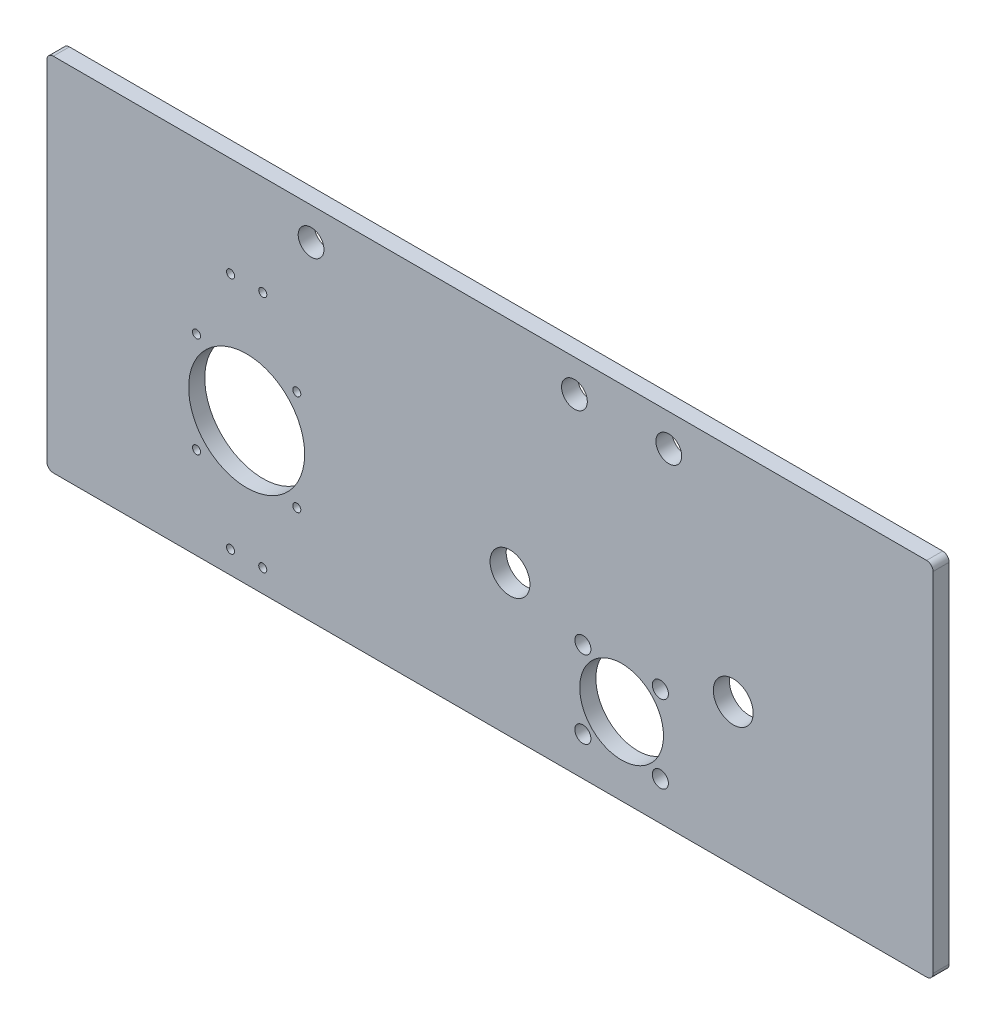
SolidWorks part; units mm, degrees
ref_plane "Спереди" through (0, 0, 0) normal (0, 0, 1) x (1, 0, 0)
ref_plane "Сверху" through (0, 0, 0) normal (0, 1, 0) x (1, 0, 0)
ref_plane "Справа" through (0, 0, 0) normal (1, 0, 0) x (0, 0, -1)
sketch "Эскиз1" plane through (0, 0, 0) normal (0, 0, 1) x (1, 0, 0)
  line L0 (-12.0208, 12.0208) -> (0, 0) construction
  line L1 (-178.359, 88) -> (96.641, 88)
  line L2 (-178.359, 88) -> (-178.359, -24)
  line L3 (-178.359, -24) -> (96.641, -24)
  line L4 (96.641, 88) -> (96.641, -24)
  line L5 (0, 0) -> (0, 88) construction
  line L6 (-34.641, 20) -> (0, 0) construction
  circle A0 centre (0, 0) radius 13
  circle A1 centre (-12.0208, 12.0208) radius 2.5
  circle A2 centre (12.0208, 12.0208) radius 2.5
  circle A3 centre (12.0208, -12.0208) radius 2.5
  circle A4 centre (-12.0208, -12.0208) radius 2.5
  circle A5 centre (-34.641, 20) radius 6.1833
  circle A6 centre (34.641, 20) radius 6.1833
  circle A7 centre (-116.359, 20) radius 18
  circle A8 centre (-14.641, 78) radius 4
  circle A9 centre (14.641, 78) radius 4
  circle A10 centre (-96.359, 78) radius 4
  circle A11 centre (-116.359, 20) radius 18 construction
  point P19 (0, 0)
  dimension "D2" = 5
  dimension "D4" = 26
  dimension "D9" = 8
  dimension "D1" = 45
  dimension "D3" = 17
  dimension "D6" = 58
  dimension "D7" = 20
  dimension "D8" = 20
  dimension "D10" = 10
  dimension "D12" = 40
  dimension "D13" = 20
  dimension "D14" = 275
  dimension "D15" = 82
  dimension "D16" = 82
  dimension "D11" = 112
  dimension "D5" = 4
extrude "Бобышка-Вытянуть1" add sketch "Эскиз1" along normal blind 5
hole_wizard "Отверстие обработанное метчиком M32" positions "Эскиз2" profile "Эскиз4" tap size "M3" standard "ISO" end condition through all
sketch "Эскиз2" plane through (0, 0, 0) normal (0, 0, -1) x (-1, 0, 0)
  point P0 (111.359, 57)
  point P3 (121.359, 57)
  point P6 (111.359, -17)
  point P9 (121.359, -17)
sketch "Эскиз4" plane through (-111.359, 57, 0) normal (1, 0, 0) x (0, 1, 0)
  line L0 (0, 0) -> (0, 5)
  line L1 (0, 5) -> (1.25, 5)
  line L2 (1.25, 5) -> (1.25, 0)
  line L5 (1.25, 0) -> (0, 0)
  line L11 (0, -6.35) -> (0, 107.95) construction
  dimension "Диаметр проходного сверла" = 2.5
  dimension "Глубина проходного сверла" = 5
cosmetic thread "Отверстие резьбы1" parameters "D2"=3
cosmetic thread "Отверстие резьбы2" parameters "D2"=3
cosmetic thread "Отверстие резьбы3" parameters "D2"=3
cosmetic thread "Отверстие резьбы4" parameters "D2"=3
fillet "Скругление1" radius 2 4 edges at (-178.359, -24, 2.5) (96.641, -24, 2.5) (96.641, 88, 2.5) (-178.359, 88, 2.5)
hole_wizard "Отверстие обработанное метчиком M35" positions "Эскиз12" profile "Эскиз13" tap size "M3" standard "DIN" end condition up to next
sketch "Эскиз12" plane through (0, 0, 5) normal (0, 0, 1) x (1, 0, 0)
  point P0 (-100.8026, 35.5563)
sketch "Эскиз13" plane through (-100.8026, 35.5563, 5) normal (1, 0, 0) x (0, -1, 0)
  line L0 (0, 0) -> (0, 5)
  line L1 (0, 5) -> (1.25, 5)
  line L2 (1.25, 5) -> (1.25, 0)
  line L5 (1.25, 0) -> (0, 0)
  line L11 (0, -6.35) -> (0, 107.95) construction
  dimension "Диаметр проходного сверла" = 2.5
  dimension "Глубина проходного сверла" = 5
pattern_circular "Круговой массив1" count 4 over 360 about axis through (-116.359, 20, 0) along (0, 0, 1) of "Отверстие обработанное метчиком M35"
sketch "Эскиз5" plane through (0, 0, 5) normal (0, 0, 1) x (1, 0, 0)
  line L0 (-178.359, 66) -> (96.641, 66)
  line L1 (-178.359, 86) -> (-178.359, -22) construction
  line L2 (96.641, -22) -> (96.641, 86) construction
  line L3 (-158.359, 78) -> (-158.359, -24)
  line L4 (-176.359, -24) -> (94.641, -24) construction
  line L5 (-76.641, 78) -> (-76.641, -24)
  line L6 (76.641, 78) -> (76.641, -24)
  circle A0 centre (14.641, 78) radius 4 construction
  circle A1 centre (14.641, 78) radius 4 construction
  circle A2 centre (14.641, 78) radius 62 construction
  circle A3 centre (-14.641, 78) radius 62 construction
  circle A4 centre (-96.359, 78) radius 62 construction
  dimension "D2" = 124
  dimension "D1" = 12
ref_plane "Плоскость1" through (0, 66, 0) normal (0, 1, 0) x (1, 0, 0)
ref_plane "Плоскость2" through (-158.359, 0, 0) normal (1, 0, 0) x (0, 0, -1)
ref_plane "Плоскость3" through (-76.641, 0, 0) normal (1, 0, 0) x (0, 0, -1)
ref_plane "Плоскость4" through (76.641, 0, 0) normal (1, 0, 0) x (0, 0, -1)
equation "\"Диаметр резьбы редуктора\" = 4  'Диаметр резьбы на фланце"
equation "\"Глубина резьбы редуктора\" = 7  'Диаметр резьбы на фланце"
equation "\"Диаметр окружности расположения редуктора\" = 34  'Диаметр расположения резьбы на фланце"
equation "\"Диаметр бурта редуктора\" = 26  'Диаметр бурта на фланце (Посадка h7)"
equation "\"Угл сдвига редуктора\" = 45"
equation "\"D1@Эскиз1\"=\"Угл сдвига редуктора\""
equation "\"D2@Эскиз1\"=\"Диаметр резьбы редуктора\"+1"
equation "\"D3@Эскиз1\"=\"Диаметр окружности расположения редуктора\"/2"
equation "\"D4@Эскиз1\"=\"Диаметр бурта редуктора\""
equation "\"Толщина пластины\" = 5"
equation "\"Межосевое прижима Вертикаль\" = 18  '!!!"
equation "\"Межосевое прижима Горизонталь\" = 20  '!!!"
equation "\"D7@Эскиз1\"=\"Межосевое прижима Горизонталь\""
equation "\"D8@Эскиз1\"=\"Межосевое прижима Горизонталь\""
equation "\"D1@Бобышка-Вытянуть1\"=\"Толщина пластины\""
equation "\"D6@Эскиз1\"=\"Межосевое прижима Вертикаль\"+\"Внешний диаметр ролика\""
equation "\"Внешний диаметр ролика\" = 40  'Внешний диаметр ролика"
equation "\"Диаметр вала ролика\" = 8  '!!!"
equation "\"D9@Эскиз1\"=\"Диаметр вала ролика\""
equation "\"D16@Эскиз1\"=\"D15@Эскиз1\""
